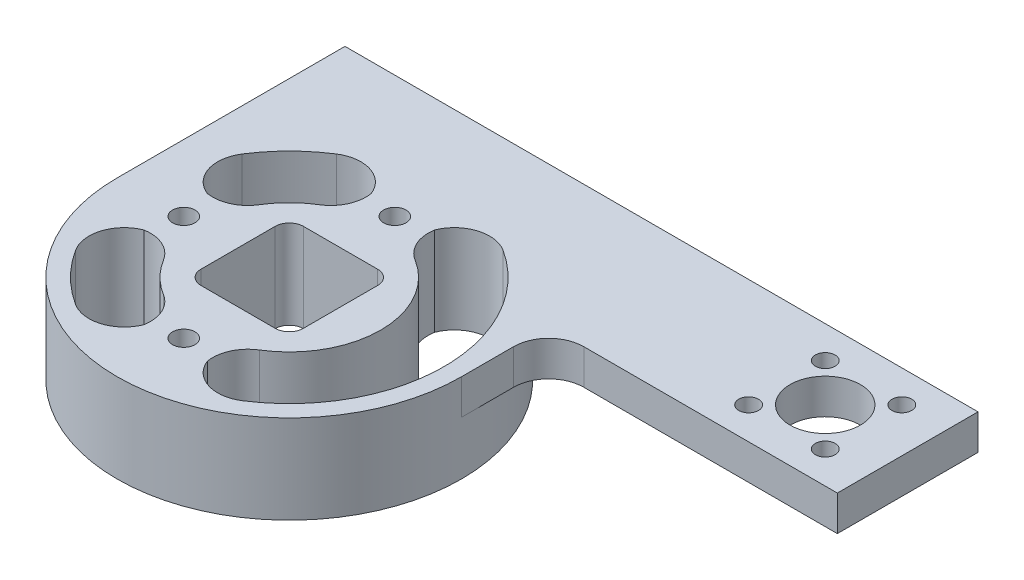
SolidWorks part; units mm, degrees
material "6061-T6 (SS)"
ref_plane "Front Plane" through (0, 0, 0) normal (0, 0, 1) x (1, 0, 0)
ref_plane "Top Plane" through (0, 0, 0) normal (0, 1, 0) x (1, 0, 0)
ref_plane "Right Plane" through (0, 0, 0) normal (1, 0, 0) x (0, 0, -1)
sketch "Sketch1" plane through (0, 0, 0) normal (0, 1, 0) x (1, 0, 0)
  line L0 (-1.1049, 0) -> (-31.0896, 0) construction
  line L1 (-1.1049, 0) -> (31.0896, 0) construction
  circle A0 centre (0, 0) radius 31.0896
  dimension "D1" = 62.1792
extrude "Boss-Extrude1" add sketch "Sketch1" along normal blind 16.002
sketch "Sketch2" plane through (0, 16.002, 0) normal (0, 1, 0) x (1, 0, 0)
  line L0 (0, 0) -> (-31.0896, 0) construction
  line L1 (0, 0) -> (31.0896, 0) construction
  line L2 (-31.0896, 0) -> (-31.0896, 41.148)
  line L3 (-31.0896, 41.148) -> (83.2104, 41.148)
  line L4 (83.2104, 41.148) -> (83.2104, 15.748)
  line L5 (31.0896, 0) -> (31.0896, 15.748)
  line L6 (31.0896, 15.748) -> (83.2104, 15.748)
  circle A0 centre (0, 0) radius 31.0896 construction
  circle A2 centre (0, 0) radius 31.0896
  arc A3 (-31.0896, 0) -> (31.0896, 0) centre (0, 0) ccw
  dimension "D1" = 0
  dimension "D2" = 114.3
  dimension "D3" = 25.4
  dimension "D4" = 15.748
extrude "Boss-Extrude2" add sketch "Sketch2" against normal blind 6.35
fillet "Fillet1" [suppressed] radius 6.35
fillet "Fillet2" radius 6.35 1 edges at (31.0896, 12.827, -15.748)
sketch "Sketch4" plane through (0, 16.002, 0) normal (0, 1, 0) x (1, 0, 0)
  line L0 (83.2104, 41.148) -> (58.166, 41.148) construction
  line L1 (83.2104, 41.148) -> (-31.0896, 41.148) construction
  line L2 (58.166, 41.148) -> (58.166, 28.448) construction
  line L3 (58.166, 28.448) -> (78.486, 28.448) construction
  line L4 (68.326, 28.448) -> (75.2408, 35.3628) construction
  line L5 (68.326, 28.448) -> (75.2408, 21.5332) construction
  line L6 (68.326, 28.448) -> (61.4112, 21.5332) construction
  line L7 (68.326, 28.448) -> (61.4112, 35.3628) construction
  circle A0 centre (61.4112, 35.3628) radius 1.778
  circle A1 centre (75.2408, 35.3628) radius 1.778
  circle A2 centre (75.2408, 21.5332) radius 1.778
  circle A3 centre (68.326, 28.448) radius 6.35
  circle A4 centre (61.4112, 21.5332) radius 1.778
extrude "Cut-Extrude2" cut sketch "Sketch4" against normal up to next
sketch "Sketch5" plane through (0, 16.002, 0) normal (0, 1, 0) x (1, 0, 0)
  line L1 (9.2497, 9.2497) -> (-9.2497, 9.2497)
  line L2 (9.2497, 9.2497) -> (9.2497, -9.2497)
  line L3 (9.2497, -9.2497) -> (-9.2497, -9.2497)
  line L4 (-9.2497, 9.2497) -> (-9.2497, -9.2497)
  line L5 (9.2497, 9.2497) -> (-9.2497, -9.2497) construction
  line L6 (9.2497, -9.2497) -> (-9.2497, 9.2497) construction
  point P0 (0, 0)
  dimension "D1" = 26.162
extrude "Cut-Extrude3" cut sketch "Sketch5" against normal up to next
fillet "Fillet3" radius 2.54 1 edges at (-9.2497, 8.001, -9.2497)
fillet "Fillet4" radius 2.54 1 edges at (9.2497, 8.001, -9.2497)
fillet "Fillet5" radius 2.54 1 edges at (9.2497, 8.001, 9.2497)
fillet "Fillet6" radius 2.54 1 edges at (-9.2497, 8.001, 9.2497)
sketch "Sketch7" plane through (0, 0, 0) normal (0, 1, 0) x (1, 0, 0)
  line L0 (0, 27.94) -> (0, -31.0896)
  line L1 (0, 0) -> (-7.4507, 26.9283)
  line L2 (-7.4507, -26.9283) -> (0, 0)
  line L3 (0, 0) -> (7.4507, 26.9283)
  line L4 (0, 0) -> (7.4507, -26.9283)
  line L5 (-26.9283, 7.4507) -> (0, 0)
  line L6 (0, 0) -> (26.9283, -7.4507) construction
  line L7 (-26.9283, -7.4507) -> (0, 0)
  line L8 (0, 0) -> (26.9283, 7.4507) construction
  line L9 (0, 0) -> (-26.2234, 0) construction
  circle A0 centre (0, 0) radius 16.51
  circle A1 centre (0, 0) radius 27.94
  circle A2 centre (0, 0) radius 31.0896 construction
  circle A3 centre (-19.05, 0) radius 2.0193
  circle A4 centre (0, 19.05) radius 2.0193
  circle A5 centre (0, -19.05) radius 2.0193
  circle A6 centre (0, 0) radius 19.05 construction
  dimension "D1" = 33.02
  dimension "D2" = 55.88
  dimension "D3" = 4.0386
  dimension "D4" = 38.1
  dimension "D5" = 5.08
  dimension "D6" = 5.08
  dimension "D7" = 5.08
  dimension "D8" = 5.08
extrude "Cut-Extrude4" cut sketch "Sketch7" along normal through all contours L4 A1 L3 A0 | L7 A1 L2 A0 | L1 A1 L5 A0 | A3 | A5 | A4 region at (16.8291, 0, 0) region at (-15.3599, 0, -15.3599) region at (-15.3599, 0, 15.3599)
fillet "Fillet7" radius 6.35 12 edges at (-26.9283, 8.001, -7.4507) (-7.4507, 8.001, -26.9283) (-4.4027, 8.001, -15.9122) (4.4027, 8.001, -15.9122) (7.4507, 8.001, -26.9283) (4.4027, 8.001, 15.9122) (7.4507, 8.001, 26.9283) (-7.4507, 8.001, 26.9283) (-4.4027, 8.001, 15.9122) (-15.9122, 8.001, 4.4027) (-26.9283, 8.001, 7.4507) (-15.9122, 8.001, -4.4027)
